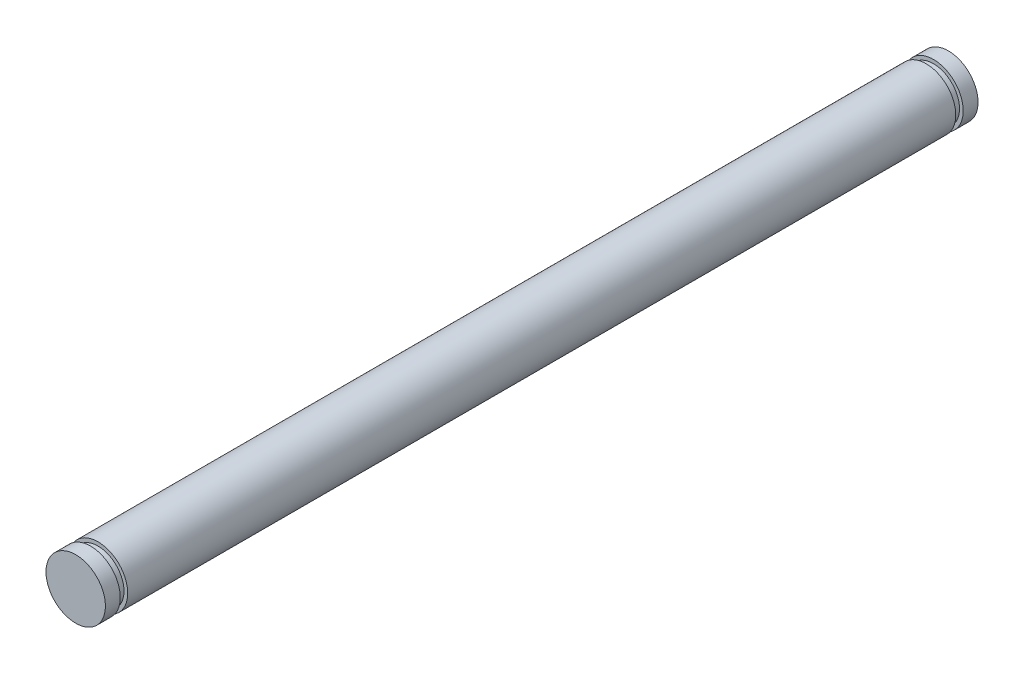
SolidWorks part; units mm, degrees
ref_plane "正面" through (0, 0, 0) normal (0, 0, 1) x (1, 0, 0)
ref_plane "平面" through (0, 0, 0) normal (0, 1, 0) x (1, 0, 0)
ref_plane "右側面" through (0, 0, 0) normal (1, 0, 0) x (0, 0, -1)
sketch "ｽｹｯﾁ1" plane through (0, 0, 0) normal (0, 0, 1) x (1, 0, 0)
  circle A0 centre (0, 0) radius 4
  dimension "D1" = 8
extrude "ﾎﾞｽ - 押し出し1" add sketch "ｽｹｯﾁ1" along normal blind 117.5
sketch "ｽｹｯﾁ2" plane through (0, 0, 0) normal (0, 1, 0) x (1, 0, 0)
  line L0 (4, -2) -> (3.5, -2)
  line L1 (4, -117.5) -> (4, 0) construction
  line L2 (3.5, -2) -> (3.5, -3)
  line L3 (3.5, -3) -> (4, -3)
  line L4 (4, -3) -> (4, -2)
  line L5 (-4.4, 0) -> (4.4, 0) construction
  line L6 (3.5, -114.5) -> (3.5, -115.5)
  line L7 (3.5, -115.5) -> (4, -115.5)
  line L8 (4, -115.5) -> (4, -114.5)
  line L9 (4, -114.5) -> (3.5, -114.5)
  line L10 (-4, -117.5) -> (4, -117.5) construction
  dimension "D1" = 2
  dimension "D2" = 1
  dimension "D3" = 0.5
  dimension "D4" = 2
  dimension "D5" = 1
  dimension "D6" = 0.5
ref_axis "軸1" through (0, 0, -5.875) along (0, 0, 1)
revolve "ｶｯﾄ - 回転1" cut sketch "ｽｹｯﾁ2" angle 360 about axis through (0, 0, 117.5) along (0, 0, -1)
equation "\"shaft_length\"= 117.5"
equation "\"D1@ﾎﾞｽ - 押し出し1\"=\"shaft_length\""
